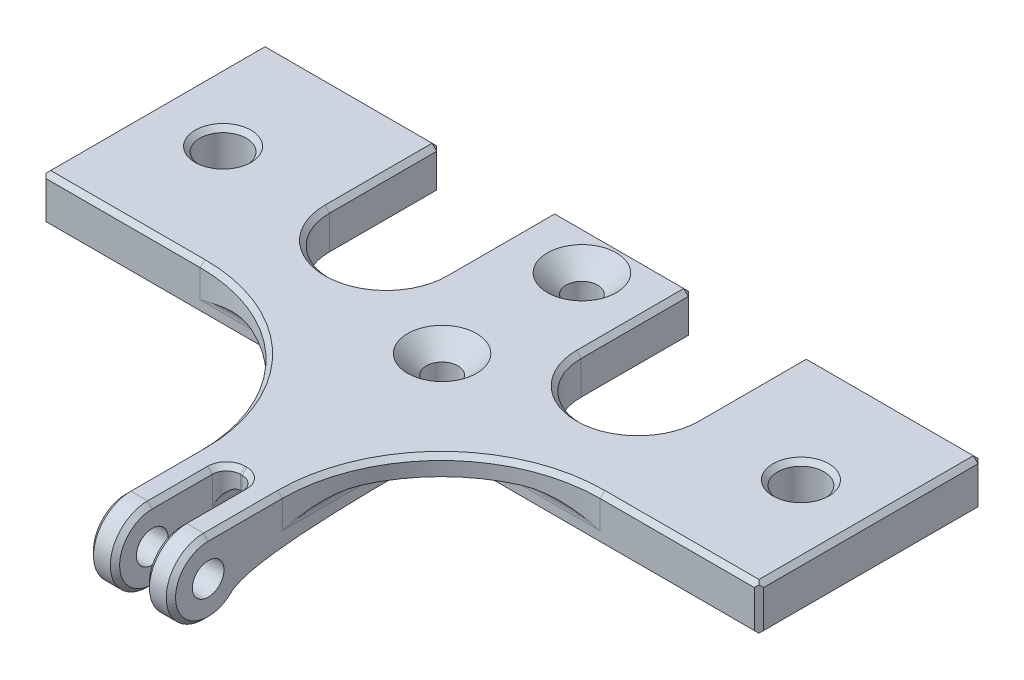
SolidWorks part; units mm, degrees
ref_plane "Front Plane" through (0, 0, 0) normal (0, 0, 1) x (1, 0, 0)
ref_plane "Top Plane" through (0, 0, 0) normal (0, 1, 0) x (1, 0, 0)
ref_plane "Right Plane" through (0, 0, 0) normal (1, 0, 0) x (0, 0, -1)
sketch "Sketch1" plane through (0, 0, 0) normal (0, 1, 0) x (1, 0, 0)
  line L0 (0, 0) -> (0, 50000) construction
  line L1 (38.5, -12) -> (-38.5, -12)
  line L2 (38.5, -12) -> (38.5, 12)
  line L3 (38.5, 12) -> (-38.5, 12)
  line L4 (-38.5, -12) -> (-38.5, 12)
  line L5 (38.5, -12) -> (-38.5, 12) construction
  line L6 (38.5, 12) -> (-38.5, -12) construction
  line L7 (0, 0) -> (50000, 0) construction
  line L8 (-19.575, 0) -> (-19.575, 12)
  line L9 (-7.425, 0) -> (-7.425, 12)
  line L10 (7.425, 0) -> (7.425, 12)
  line L11 (19.575, 0) -> (19.575, 12)
  circle A0 centre (-31, 0) radius 2.5
  circle A1 centre (-13.5, 0) radius 6.075
  circle A2 centre (31, 0) radius 2.5
  circle A3 centre (13.5, 0) radius 6.075
  circle A4 centre (0, -7.5) radius 1.7
  circle A5 centre (0, 7.5) radius 1.7
  point P0 (0, 0)
  dimension "D3" = 27
  dimension "D5" = 5
  dimension "D6" = 12.15
  dimension "D7" = 3.4
  dimension "D1" = 24
  dimension "D2" = 77
  dimension "D4" = 62
  dimension "D8" = 7.5
  dimension "D9" = 7.5
extrude "Boss-Extrude1" add sketch "Sketch1" along normal blind 5 contours L11 A3 L10 L3 L9 A1 L8 L4 L1 L2 A2 A0 region at (0, 0, 1.0489)
chamfer "Chamfer2" distance 2 angle 45 2 edges at (0, 5, -5.8) (0, 5, 9.2)
sketch "Sketch2" plane through (0, 0, 0) normal (0, -1, 0) x (1, 0, 0)
  line L9 (-5.025, 0) -> (-5.025, -12)
  line L10 (-21.975, -12) -> (-21.975, 0)
  line L11 (-5.025, 0) -> (-5.025, -12)
  line L12 (-21.975, -12) -> (-21.975, 0)
  line L14 (21.975, -12) -> (5.025, -12)
  line L15 (-5.025, -12) -> (-21.975, -12)
  line L16 (21.975, 0) -> (21.975, -12)
  line L17 (5.025, -12) -> (5.025, 0)
  line L18 (21.975, 0) -> (21.975, -12)
  line L19 (5.025, -12) -> (5.025, 0)
  arc A7 (-5.025, 0) -> (-21.975, 0) centre (-13.5, 0) ccw
  arc A8 (-5.025, 0) -> (-21.975, 0) centre (-13.5, 0) ccw
  arc A12 (21.975, 0) -> (5.025, 0) centre (13.5, 0) ccw
  arc A13 (21.975, 0) -> (5.025, 0) centre (13.5, 0) ccw
  dimension "D1" = 2.4
  dimension "D2" = 2.4
extrude "Cut-Extrude1" cut sketch "Sketch2" against normal blind 0.4
chamfer "Chamfer3" distance 0.5 angle 45 44 edges at (-31, 0, 2.5) (-31, 5, 2.5) (31, 0, 2.5) (31, 5, 2.5) (19.575, 5, -6) (7.425, 5, -6) (13.5, 5, 6.075) (38.5, 5, 0) (38.5, 2.5, 12) (-38.5, 5, 0) (-38.5, 2.5, 12) (-19.575, 2.7, -12) (-29.0375, 5, -12) (-38.5, 2.5, -12) (-30.2375, 0, -12) (-38.5, 0, 0) (38.5, 0, 0) (38.5, 2.5, -12) (29.0375, 5, -12) (19.575, 2.7, -12) (30.2375, 0, -12) (7.425, 2.7, -12) (0, 5, -12) (-7.425, 2.7, -12) (-19.575, 5, -6) (-7.425, 5, -6) (-13.5, 5, 6.075) (0, 0, 9.2) (0, 0, -5.8) (7.425, 0.4, -6) (19.575, 0.4, -6) (13.5, 0.4, 6.075) (-20.775, 0.4, -12) (-21.975, 0.2, -12) (20.775, 0.4, -12) (21.975, 0.2, -12) (5.025, 0.2, -12) (6.225, 0.4, -12) (-6.225, 0.4, -12) (-5.025, 0.2, -12) (0, 0, -12) (-7.425, 0.4, -6) (-19.575, 0.4, -6) (-13.5, 0.4, 6.075)
sketch "Sketch4" plane through (0, 0, 0) normal (1, 0, 0) x (0, 0, -1)
  line L0 (-12, 0) -> (-12, 5) construction
  line L1 (-12, 5) -> (11.5, 5) construction
  line L2 (-37, 5) -> (-12, 5)
  line L3 (-12, 5) -> (-12, 0)
  line L5 (-36.9087, -4.4289) -> (-31.3424, 0.8557) construction
  line L6 (-16.8153, 0) -> (-7.1847, 0) construction
  arc A0 (-37, 5) -> (-34.2459, -1.9009) centre (-37, 1) ccw
  circle A1 centre (-37, 1) radius 1.7
  spline S0 degree 3 poles (-12, 0) (-18.0192, 0) (-32.1175, 0.1198) (-34.2459, -1.9009) knots 0 0 0 0 1 1 1 1
  dimension "D1" = 8
  dimension "D2" = 3.4
  dimension "D3" = 25
extrude "Boss-Extrude3" add sketch "Sketch4" along normal blind 2.8 from offset 1.6
extrude "Boss-Extrude4" add sketch "Sketch4<2>" against normal blind 2.8 from offset 1.6 offset against normal yes
sketch "Sketch4<2>" plane through (0, 0, 0) normal (1, 0, 0) x (0, 0, -1) same geometry as "Sketch4"
sketch "Sketch5" plane through (0, 5, 0) normal (0, 1, 0) x (1, 0, 0)
  line L1 (-4.4, -12) -> (-38, -12) construction
  line L6 (38.5, 11.5) -> (38.5, -11.5) construction
  line L7 (4.4, -12) -> (4.4, -37) construction
  line L10 (-4.4, -12) -> (-4.4, -37) construction
  line L11 (4.4, -29.05) -> (-4.4, -29.05)
  line L12 (-21.45, -12) -> (21.45, -12)
  circle A0 centre (21.45, -29.05) radius 17.05
  circle A1 centre (-21.45, -29.05) radius 17.05
  circle A2 centre (0, -7.5) radius 3.7 construction
  spline S0 degree 1 poles (-2.8956, -9.8034) (-2.9506, -10.8774) knots 0 0 1 1
  line M14 (-4.4, -12) -> (-4.4, -37)
  line M16 (-1.6, -37) -> (-1.6, -12)
  line M18 (1.6, -12) -> (1.6, -37)
  line M20 (4.4, -37) -> (4.4, -12)
extrude "Boss-Extrude5" add sketch "Sketch5" against normal blind 2 contours L12 L11 M18 M20 | L12 L11 M16 M18 | L12 L11 M14 M16 | A1 L12 M14 | A0 L12 M20 region at (8.2084, 5, 15.8084) region at (3, 5, 20.525) region at (0, 5, 20.525) region at (-3, 5, 20.525) region at (-8.2084, 5, 15.8084)
fillet "Fillet1" radius 1.5 9 edges at (-1.6, 3, 20.525) (0, 3, 12) (1.6, 3, 20.525) (-12.925, 3, 12) (-4.4, 3, 20.525) (12.925, 3, 12) (4.4, 3, 20.525) (1.6, 4, 29.05) (-1.6, 4, 29.05)
chamfer "Chamfer4" distance 0.5 angle 45 22 edges at (-1.6, -0.4826, 40.7151) (-1.6, 5, 33.775) (-1.1607, 5, 29.4893) (0, 5, 29.05) (1.1607, 5, 29.4893) (1.6, -0.4826, 40.7151) (-4.4, -0.4826, 40.7151) (-4.4, 5, 33.025) (-9.3938, 5, 16.9938) (4.4, -0.4826, 40.7151) (9.3938, 5, 16.9938)
